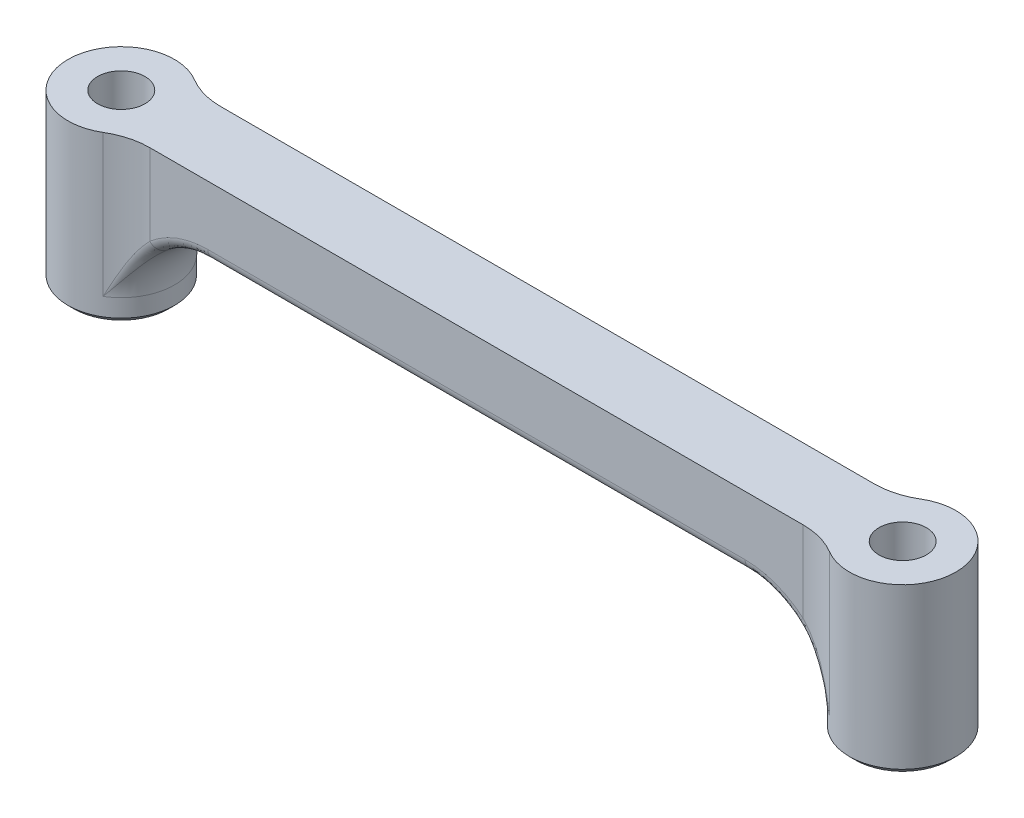
SolidWorks part; units mm, degrees
ref_plane "Front Plane" through (0, 0, 0) normal (0, 0, 1) x (1, 0, 0)
ref_plane "Top Plane" through (0, 0, 0) normal (0, 1, 0) x (1, 0, 0)
ref_plane "Right Plane" through (0, 0, 0) normal (1, 0, 0) x (0, 0, -1)
sketch "Sketch1" plane through (0, 0, 0) normal (0, 1, 0) x (1, 0, 0)
  line L1 (-14.8229, 1.5) -> (0, 1.5)
  line L2 (-14.8229, 1.5) -> (-14.8229, -1.5)
  line L3 (-14.8229, -1.5) -> (0, -1.5)
  line L4 (0, 1.5) -> (0, -1.5)
  circle A0 centre (-16.5, 0) radius 1
  circle A1 centre (-16.5, 0) radius 2.25
  point P8 (0, 0)
  point P9 (0, 0)
  point P10 (-14.6495, 1.2799)
  dimension "D2" = 2
  dimension "D3" = 4.5
  dimension "D1" = 16.5
  dimension "D4" = 3
extrude "Boss-Extrude1" add sketch "Sketch1" along normal blind 3 contours A1 L3 L4 L1 | L2 A1 A0 | L2 A1 region at (-14.5911, 0, 0) region at (-7.216, 0, 0) region at (-14.8827, 0, 0)
extrude "Boss-Extrude2" add sketch "Sketch1<3>" against normal blind 4 contours L2 A1 | L2 A1 A0 region at (-14.5911, 0, 0) region at (-14.8827, 0, 0)
sketch "Sketch1<3>" plane through (0, 0, 0) normal (0, 1, 0) x (1, 0, 0) same geometry as "Sketch1"
fillet "Fillet1" radius 3 3 edges at (-14.25, 0, 0) (-14.8229, 1.5, -1.5) (-14.8229, 1.5, 1.5)
mirror "Mirror1" about plane through (0, 3, 0) normal (1, 0, 0) of bodies 103
fillet "Fillet2" radius 0.5 10 edges at (-14.7476, -2.0323, -1.655) (-12.7813, -0.2684, -1.5) (14.7476, -2.0323, -1.655) (12.7813, -0.2684, -1.5) (-14.7476, -2.0323, 1.655) (-12.7756, -0.266, 1.5) (14.7476, -2.0323, 1.655) (12.7756, -0.266, 1.5) (0, 0, -1.5) (0, 0, 1.5)
chamfer "Chamfer1" distance 0.25 angle 45 2 edges at (-16.5, -4, 2.25) (16.5, -4, 2.25)
